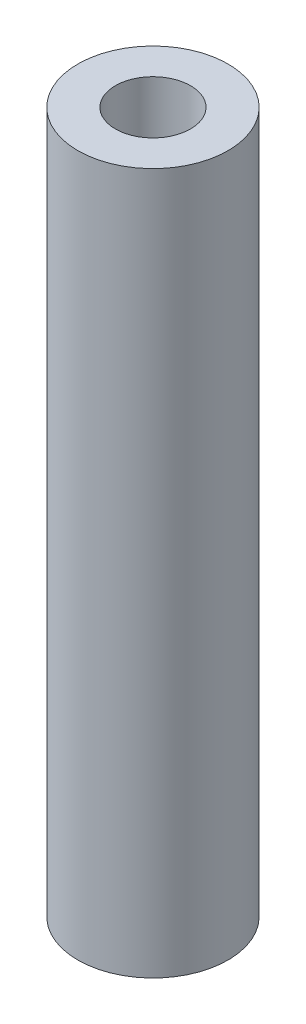
SolidWorks part; units mm, degrees
ref_plane "Front Plane" through (0, 0, 0) normal (0, 0, 1) x (1, 0, 0)
ref_plane "Top Plane" through (0, 0, 0) normal (0, 1, 0) x (1, 0, 0)
ref_plane "Right Plane" through (0, 0, 0) normal (1, 0, 0) x (0, 0, -1)
sketch "Sketch2" plane through (0, 0, 0) normal (0, 1, 0) x (1, 0, 0)
  circle A0 centre (-15.0841, 6.4658) radius 1.5
  circle A1 centre (-15.0841, 6.4658) radius 3
  dimension "D1" = 3
  dimension "D2" = 6
extrude "Boss-Extrude1" add sketch "Sketch2" along normal blind 28
